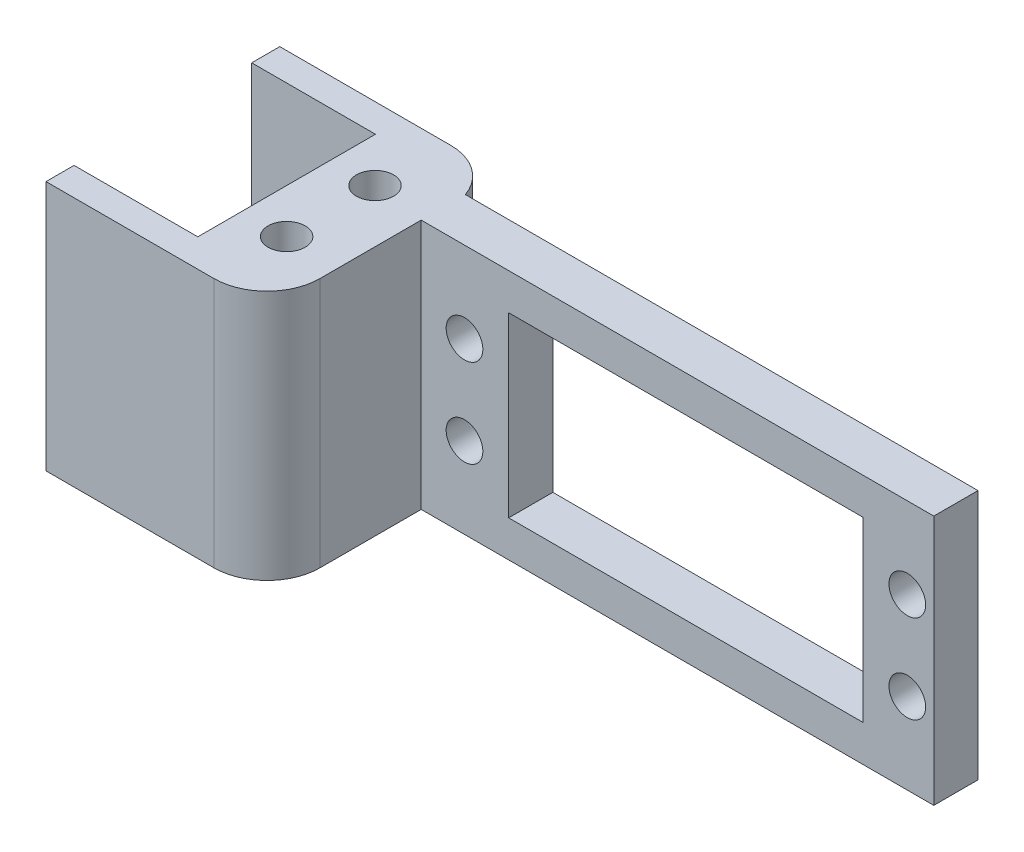
SolidWorks part; units mm, degrees
ref_plane "Front Plane" through (0, 0, 0) normal (0, 0, 1) x (1, 0, 0)
ref_plane "Top Plane" through (0, 0, 0) normal (0, 1, 0) x (1, 0, 0)
ref_plane "Right Plane" through (0, 0, 0) normal (1, 0, 0) x (0, 0, -1)
sketch "Sketch1" plane through (0, 0, 0) normal (0, 1, 0) x (1, 0, 0)
  line L0 (0, 0) -> (14, 0)
  line L1 (14, 0) -> (14, -20.1)
  line L2 (14, -20.1) -> (0, -20.1)
  line L3 (0, -20.1) -> (0, -23.275)
  line L4 (0, -23.275) -> (25, -23.275)
  line L5 (25, -23.275) -> (25, 3.175)
  line L6 (25, 3.175) -> (0, 3.175)
  line L7 (0, 3.175) -> (0, 0)
  line L8 (19, -5.05) -> (19, -15.05) construction
  circle A0 centre (19, -5.05) radius 2.1
  circle A1 centre (19, -15.05) radius 2.1
  point P13 (19, -10.05)
  point P14 (14, -10.05)
  point P15 (0, 0)
  point P16 (19, -1.7598)
  dimension "D1" = 4.2
  dimension "D2" = 10
  dimension "D3" = 3.175
  dimension "D4" = 14
  dimension "D5" = 5
  dimension "D6" = 20.1
  dimension "D7" = 25
extrude "Boss-Extrude1" add sketch "Sketch1" along normal blind 28.35
sketch "Sketch2" plane through (25, 0, 0) normal (1, 0, 0) x (0, 0, -1)
  line L0 (3.175, 28.35) -> (3.175, 0) construction
  line L1 (-0.825, 28.35) -> (-5.825, 28.35)
  line L2 (-0.825, 28.35) -> (-0.825, 0)
  line L3 (-0.825, 0) -> (-5.825, 0)
  line L4 (-5.825, 28.35) -> (-5.825, 0)
  line L5 (-0.825, 28.35) -> (-5.825, 0) construction
  line L6 (-0.825, 0) -> (-5.825, 28.35) construction
  line L7 (-23.275, 28.35) -> (3.175, 28.35) construction
  point P0 (-3.325, 14.175)
  point P5 (3.175, 14.175)
  point P6 (0, 0)
  dimension "D1" = 4
  dimension "D2" = 5
extrude "Boss-Extrude2" add sketch "Sketch2" along normal blind 58
sketch "Sketch3" plane through (0, 0, 0.825) normal (0, 0, -1) x (-1, 0, 0)
  line L0 (-83, 0) -> (-83, 28.35) construction
  line L1 (-34.9, 4.125) -> (-75, 4.125)
  line L2 (-34.9, 4.125) -> (-34.9, 24.225)
  line L3 (-34.9, 24.225) -> (-75, 24.225)
  line L4 (-75, 4.125) -> (-75, 24.225)
  line L5 (-34.9, 4.125) -> (-75, 24.225) construction
  line L6 (-34.9, 24.225) -> (-75, 4.125) construction
  line L7 (-83, 0) -> (-83, 28.35) construction
  point P0 (-54.95, 14.175)
  point P5 (-83, 14.175)
  point P6 (0, 0)
  dimension "D1" = 20.1
  dimension "D2" = 40.1
  dimension "D3" = 8
extrude "Cut-Extrude1" cut sketch "Sketch3" against normal through all both and the other way through all
sketch "Sketch4" plane through (0, 0, 0.825) normal (0, 0, -1) x (-1, 0, 0)
  arc A0 (-81.8181, 18.175) -> (-81.8181, 20.175) centre (-80, 19.175) ccw construction
  arc A1 (-81.8181, 8.175) -> (-81.8181, 10.175) centre (-80, 9.175) ccw construction
  arc A2 (-28.0819, 20.175) -> (-28.0819, 18.175) centre (-29.9, 19.175) ccw construction
  arc A3 (-28.0819, 10.175) -> (-28.0819, 8.175) centre (-29.9, 9.175) ccw construction
  arc A4 (-81.8181, 18.175) -> (-81.8181, 20.175) centre (-80, 19.175) ccw construction
  arc A5 (-81.8181, 8.175) -> (-81.8181, 10.175) centre (-80, 9.175) ccw construction
  arc A6 (-28.0819, 20.175) -> (-28.0819, 18.175) centre (-29.9, 19.175) ccw construction
  arc A7 (-28.0819, 10.175) -> (-28.0819, 8.175) centre (-29.9, 9.175) ccw construction
  circle A8 centre (-29.9, 19.175) radius 2.075
  circle A9 centre (-29.9, 9.175) radius 2.075
  circle A10 centre (-80, 19.175) radius 2.075
  circle A11 centre (-80, 9.175) radius 2.075
extrude "Cut-Extrude2" cut sketch "Sketch4" against normal through all both and the other way through all
fillet "Fillet1" radius 6 2 edges at (25, 14.175, 23.275) (25, 14.175, -3.175)
